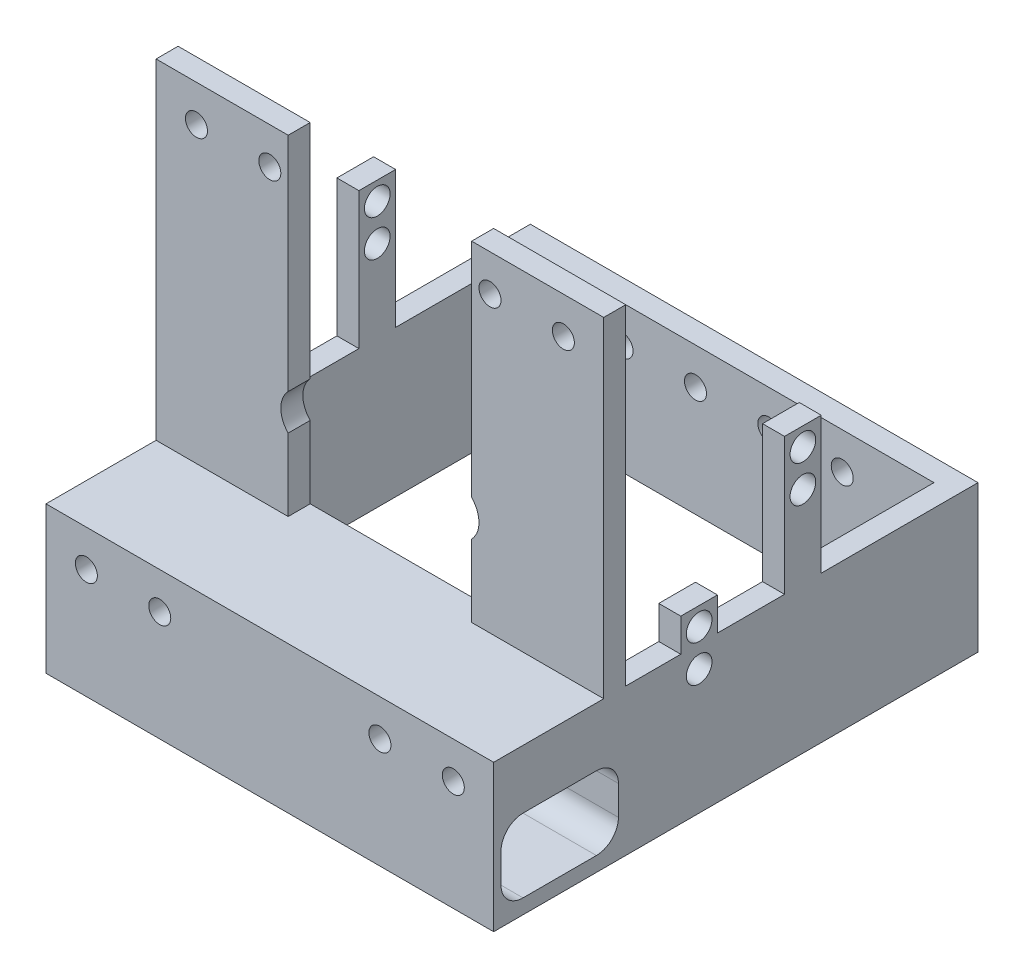
SolidWorks part; units mm, degrees
ref_plane "Front Plane" through (0, 0, 0) normal (0, 0, 1) x (1, 0, 0)
ref_plane "Top Plane" through (0, 0, 0) normal (0, 1, 0) x (1, 0, 0)
ref_plane "Right Plane" through (0, 0, 0) normal (1, 0, 0) x (0, 0, -1)
sketch "Sketch1" plane through (0, 0, 0) normal (0, 0, 1) x (1, 0, 0)
  line L1 (0, 0) -> (-55, 0)
  line L2 (0, 0) -> (0, 10)
  line L3 (0, 10) -> (-55, 10)
  line L4 (-55, 0) -> (-55, 10)
  circle A4 centre (-2.5, 5) radius 1.5
  circle A5 centre (-12.5, 5) radius 1.5
  circle A6 centre (-42.5, 5) radius 1.5
  circle A7 centre (-52.5, 5) radius 1.5
  dimension "D3" = 3
  dimension "D1" = 55
  dimension "D2" = 10
extrude "Boss-Extrude1" add sketch "Sketch1" along normal blind 15
sketch "Sketch2" plane through (0, 0, 0) normal (0, 0, -1) x (-1, 0, 0)
  line L0 (55, 10) -> (55, 0) construction
  line L1 (0, 0) -> (15, 0)
  line L2 (0, 0) -> (0, 55)
  line L3 (0, 55) -> (15, 55)
  line L4 (15, 0) -> (15, 55)
  line L5 (55, 0) -> (40, 0)
  line L6 (55, 0) -> (55, 55)
  line L7 (55, 55) -> (40, 55)
  line L8 (40, 0) -> (40, 55)
  line L9 (15, 0) -> (40, 0)
  line L10 (0, 10) -> (55, 10) construction
  line L11 (0, 10) -> (55, 10)
  circle A0 centre (12.5, 50) radius 1.5 construction
  circle A1 centre (2.5, 50) radius 1.5 construction
  circle A2 centre (2.5, 5) radius 1.5 construction
  circle A3 centre (12.5, 5) radius 1.5 construction
  circle A4 centre (52.5, 5) radius 1.5 construction
  circle A5 centre (42.5, 5) radius 1.5 construction
  circle A6 centre (52.5, 50) radius 1.5 construction
  circle A7 centre (42.5, 50) radius 1.5 construction
  circle A8 centre (12.5, 50) radius 1.5
  circle A9 centre (2.5, 50) radius 1.5
  circle A10 centre (2.5, 5) radius 1.5
  circle A11 centre (12.5, 5) radius 1.5
  circle A12 centre (52.5, 5) radius 1.5
  circle A13 centre (42.5, 5) radius 1.5
  circle A14 centre (52.5, 50) radius 1.5
  circle A15 centre (42.5, 50) radius 1.5
  circle A16 centre (17.5, 22.3) radius 3.5
  circle A17 centre (37.5, 22.3) radius 3.5
  line M9 (0, 10) -> (0, 0)
  line M10 (0, 0) -> (55, 0)
  line M11 (55, 0) -> (55, 10)
  line M12 (55, 10) -> (0, 10)
  circle M13 centre (2.5, 5) radius 1.5
  circle M14 centre (12.5, 5) radius 1.5
  circle M15 centre (42.5, 5) radius 1.5
  circle M16 centre (52.5, 5) radius 1.5
extrude "Boss-Extrude2" add sketch "Sketch2" along normal blind 3 contours L8 L4 M10 M12 | A16 L4 L3 L2 A9 A8 M12 | L4 M10 M12 M9 M14 M13 | L8 M10 M11 M12 M15 M16 | A17 L8 L6 L7 A15 A14 M12 region at (-7.5, 5, 0) region at (-27.5, 5, 0) region at (-7.4636, 32.176, 0) region at (-47.5, 5, 0) region at (-47.5364, 32.176, 0)
sketch "Sketch3" plane through (0, 0, 0) normal (0, -1, 0) x (1, 0, 0)
  line L4 (-55, 15) -> (-55, -3)
  line L5 (-55, -3) -> (0, -3)
  line L6 (0, -3) -> (0, 15)
  line L7 (0, 15) -> (-55, 15)
  line L8 (-55, 15) -> (-55, -3)
  line L9 (-55, -3) -> (0, -3)
  line L10 (0, -3) -> (0, 15)
  line L11 (0, 15) -> (-55, 15)
  dimension "D1" = 0
extrude "Boss-Extrude3" add sketch "Sketch3" along normal blind 10
sketch "Sketch6" plane through (0, 0, 0) normal (1, 0, 0) x (0, 0, -1)
  line L6 (-15, 10) -> (-15, -10)
  line L7 (-15, -10) -> (3, -10)
  line L8 (3, -10) -> (3, 55)
  line L9 (3, 55) -> (0, 55)
  line L10 (0, 55) -> (0, 10)
  line L11 (0, 10) -> (-15, 10)
  line L12 (-15, 10) -> (-15, -10)
  line L13 (-15, -10) -> (3, -10)
  line L14 (3, -10) -> (3, 55)
  line L15 (3, 55) -> (0, 55)
  line L16 (0, 55) -> (0, 10)
  line L17 (0, 10) -> (-15, 10)
  dimension "D1" = 0
extrude "Boss-Extrude5" add sketch "Sketch6" along normal blind 3
sketch "Sketch8" plane through (-55, 0, 0) normal (-1, 0, 0) x (0, 0, 1)
  line L6 (15, 10) -> (0, 10)
  line L7 (0, 10) -> (0, 55)
  line L8 (0, 55) -> (-3, 55)
  line L9 (-3, 55) -> (-3, -10)
  line L10 (-3, -10) -> (15, -10)
  line L11 (15, -10) -> (15, 10)
  line L12 (15, 10) -> (0, 10)
  line L13 (0, 10) -> (0, 55)
  line L14 (0, 55) -> (-3, 55)
  line L15 (-3, 55) -> (-3, -10)
  line L16 (-3, -10) -> (15, -10)
  line L17 (15, -10) -> (15, 10)
  dimension "D1" = 0
extrude "Boss-Extrude6" add sketch "Sketch8" along normal blind 3
sketch "Sketch9" plane through (-58, 0, 0) normal (-1, 0, 0) x (0, 0, 1)
  line L0 (15, -10) -> (15, 10) construction
  line L1 (1, -8) -> (11, -8)
  line L2 (-2, -5) -> (-2, -1)
  line L3 (1, 2) -> (11, 2)
  line L4 (14, -5) -> (14, -1)
  line L5 (-3, 55) -> (-3, -10) construction
  line L6 (-3, -10) -> (15, -10) construction
  arc A0 (1, -8) -> (-2, -5) centre (1, -5) cw
  arc A1 (11, -8) -> (14, -5) centre (11, -5) ccw
  arc A2 (11, 2) -> (14, -1) centre (11, -1) cw
  arc A3 (-2, -1) -> (1, 2) centre (1, -1) cw
  dimension "D5" = 3
  dimension "D1" = 1
  dimension "D2" = 1
  dimension "D3" = 2
  dimension "D4" = 10
extrude "Cut-Extrude2" cut sketch "Sketch9" against normal through all
sketch "Sketch10" plane through (0, 0, -3) normal (0, 0, -1) x (-1, 0, 0)
  line L1 (58, -10) -> (55, -10)
  line L2 (58, -10) -> (58, 10)
  line L3 (58, 10) -> (55, 10)
  line L4 (55, -10) -> (55, 10)
  line L5 (-3, -10) -> (0, -10)
  line L6 (-3, -10) -> (-3, 10)
  line L7 (-3, 10) -> (0, 10)
  line L8 (0, -10) -> (0, 10)
  dimension "D1" = 20
  dimension "D2" = 3
  dimension "D3" = 3
  dimension "D4" = 20
extrude "Boss-Extrude7" add sketch "Sketch10" along normal blind 45
ref_plane "Plane1" through (-27.5, 0, 0) normal (-1, 0, 0) x (0, 0, 1)
sketch "Sketch11" plane through (-58, 0, 0) normal (-1, 0, 0) x (0, 0, 1)
  line L0 (-48, 10) -> (-3, 10) construction
  line L1 (-3, 55) -> (-3, 10) construction
  circle A0 centre (-13, 7) radius 1.75
  dimension "D1" = 3.5
  dimension "D2" = 3
  dimension "D3" = 10
extrude "Cut-Extrude3" cut sketch "Sketch11" against normal through all
sketch "Sketch12" plane through (-58, 0, 0) normal (-1, 0, 0) x (0, 0, 1)
  line L0 (-48, 10) -> (-3, 10) construction
  line L1 (-24.64, 10) -> (-29.64, 10)
  line L2 (-24.64, 10) -> (-24.64, 28.64)
  line L3 (-24.64, 28.64) -> (-29.64, 28.64)
  line L4 (-29.64, 10) -> (-29.64, 28.64)
  line L6 (-10.5, 10) -> (-15.5, 10)
  line L7 (-10.5, 10) -> (-10.5, 14.5)
  line L8 (-10.5, 14.5) -> (-15.5, 14.5)
  line L9 (-15.5, 10) -> (-15.5, 14.5)
  circle A0 centre (-27.14, 26.14) radius 1.75
  circle A2 centre (-13, 12) radius 1.75
  circle A3 centre (-13, 7) radius 1.75 construction
  circle A4 centre (-27.14, 21.14) radius 1.75
  dimension "D1" = 3.5
  dimension "D3" = 2.5
  dimension "D4" = 14.14
  dimension "D5" = 14.14
  dimension "D6" = 2.5
  dimension "D7" = 2.5
  dimension "D8" = 2.5
  dimension "D10" = 5
  dimension "D11" = 5
  dimension "D2" = 5
  dimension "D9" = 5
extrude "Boss-Extrude8" add sketch "Sketch12" against normal blind 3
mirror "Mirror1" about plane through (-27.5, 0, 0) normal (-1, 0, 0) of "Boss-Extrude8"
sketch "Sketch13" plane through (0, 0, -48) normal (0, 0, -1) x (-1, 0, 0)
  line L0 (27.5, -34.65) -> (27.5, 34.65) construction
  line L1 (-3, -10) -> (58, -10)
  line L2 (-3, -10) -> (-3, 10)
  line L3 (-3, 10) -> (58, 10)
  line L4 (58, -10) -> (58, 10)
  circle A0 centre (22.5, 5) radius 1.5
  circle A1 centre (12.5, 5) radius 1.5
  circle A2 centre (2.5, 5) radius 1.5
  circle A3 centre (52.5, 5) radius 1.5
  circle A4 centre (42.5, 5) radius 1.5
  circle A5 centre (32.5, 5) radius 1.5
  dimension "D1" = 3
  dimension "D2" = 5
  dimension "D4" = 5
  dimension "D3" = 3
extrude "Boss-Extrude9" add sketch "Sketch13" along normal blind 3
